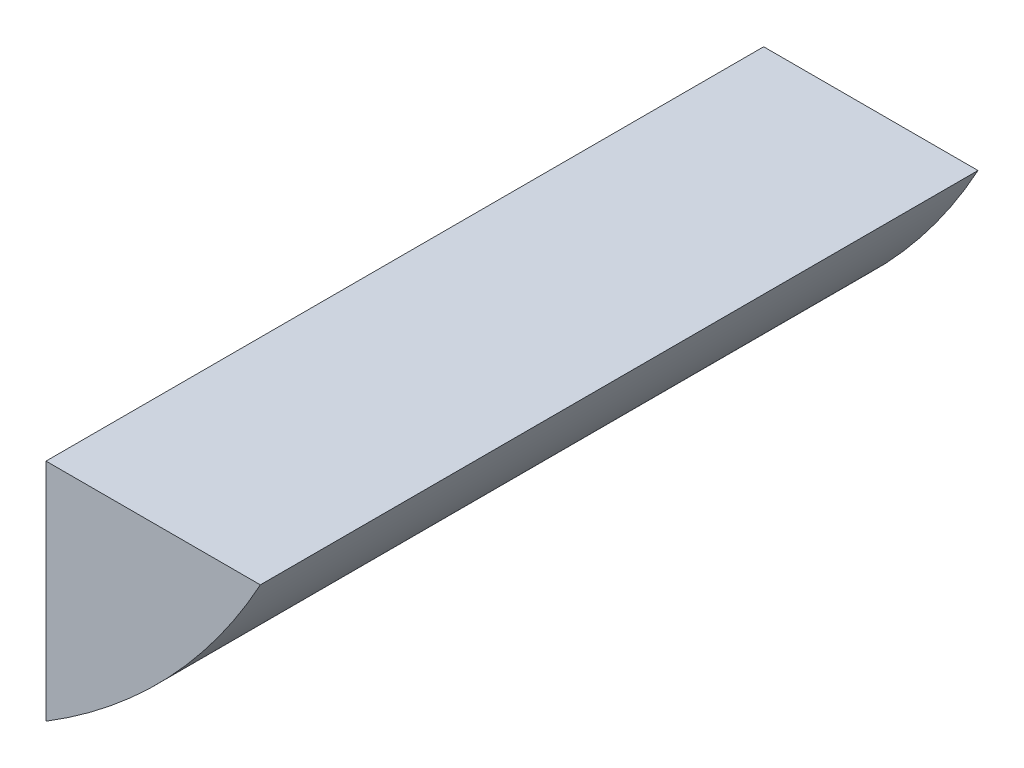
SolidWorks part; units mm, degrees
material "ABS"
ref_plane "Płaszczyzna przednia" through (0, 0, 0) normal (0, 0, 1) x (1, 0, 0)
ref_plane "Płaszczyzna górna" through (0, 0, 0) normal (0, 1, 0) x (1, 0, 0)
ref_plane "Płaszczyzna prawa" through (0, 0, 0) normal (1, 0, 0) x (0, 0, -1)
sketch "Szkic1" plane through (0, 0, 0) normal (0, 0, 1) x (1, 0, 0)
  line L7 (15.9573, -36.0859) -> (18.0264, -34.8795)
  line L13 (18.0264, -54.1634) -> (18.0264, -20.1634) construction
  line L14 (32.9596, -19.1815) -> (18.0264, -19.1815)
  line L15 (18.0264, -19.1815) -> (18.0264, -34.8795)
  arc A7 (18.0264, -34.8795) -> (32.9596, -19.1815) centre (-3.9829, 1.0093) ccw
extrude "Dodanie-wyciągnięcie1" add sketch "Szkic1" along normal blind 50 contours L7 A7 L14 L15 region at (23.4367, -24.8627, 0)
